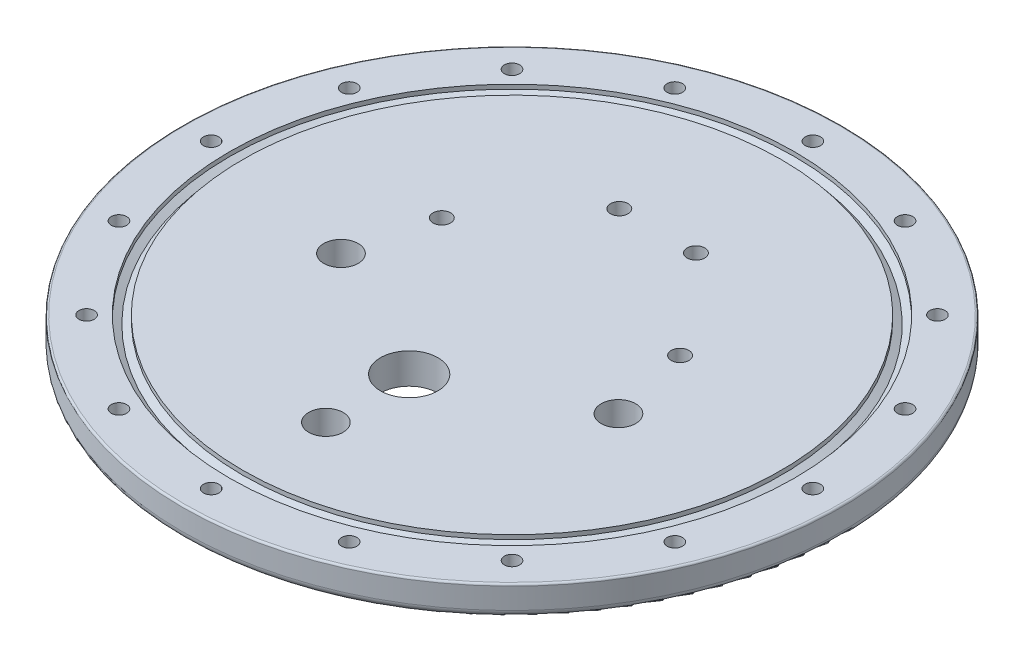
SolidWorks part; units mm, degrees
ref_plane "Front Plane" through (0, 0, 0) normal (0, 0, 1) x (1, 0, 0)
ref_plane "Top Plane" through (0, 0, 0) normal (0, 1, 0) x (1, 0, 0)
ref_plane "Right Plane" through (0, 0, 0) normal (1, 0, 0) x (0, 0, -1)
sketch "Sketch1" plane through (0, 0, 0) normal (0, 1, 0) x (1, 0, 0)
  circle A0 centre (0, 0) radius 86
  dimension "D1" = 172
extrude "Boss-Extrude1" add sketch "Sketch1" along normal blind 8 contours A0
sketch "Sketch2" plane through (0, 8, 0) normal (0, 1, 0) x (1, 0, 0)
  circle A1 centre (0, 78.5) radius 2
  circle A2 centre (30.0406, 72.5245) radius 2
  circle A3 centre (55.5079, 55.5079) radius 2
  circle A4 centre (72.5245, 30.0406) radius 2
  circle A5 centre (78.5, 0) radius 2
  circle A6 centre (72.5245, -30.0406) radius 2
  circle A7 centre (55.5079, -55.5079) radius 2
  circle A8 centre (30.0406, -72.5245) radius 2
  circle A9 centre (0, -78.5) radius 2
  circle A10 centre (-30.0406, -72.5245) radius 2
  circle A11 centre (-55.5079, -55.5079) radius 2
  circle A12 centre (-72.5245, -30.0406) radius 2
  circle A13 centre (-78.5, 0) radius 2
  circle A14 centre (-72.5245, 30.0406) radius 2
  circle A15 centre (-55.5079, 55.5079) radius 2
  circle A16 centre (-30.0406, 72.5245) radius 2
  circle A18 centre (0, 0) radius 78.5 construction
  point P38 (0, 0)
  dimension "D1" = 157
  dimension "D2" = 4
  dimension "D3" = 16
extrude "Cut-Extrude1" cut sketch "Sketch2" against normal up to next
sketch "Sketch6" plane through (0, 8, 0) normal (0, 1, 0) x (1, 0, 0)
  circle A0 centre (-10, 38) radius 2.3
  circle A1 centre (10, 38) radius 2.3
  circle A2 centre (-31.088, 12.7711) radius 2.3
  circle A3 centre (31.0922, 12.7711) radius 2.3
  dimension "D1" = 4.6
extrude "Cut-Extrude3" cut sketch "Sketch6" against normal offset from surface (6 mm away) 2 up to face at (0, 0, -76.5)
sketch "Sketch8" plane through (0, 8, 0) normal (0, 1, 0) x (1, 0, 0)
  circle A0 centre (-36.2, -8.4288) radius 4.5
  circle A1 centre (36.2, -8.4288) radius 4.5
  circle A2 centre (0, -48.5665) radius 4.5
  circle A3 centre (0, -26.8268) radius 7.5
  point P10 (0, -26.8268)
  dimension "D1" = 9
  dimension "D2" = 9
  dimension "D3" = 15
extrude "Cut-Extrude4" cut sketch "Sketch8" against normal up to next
sketch "Sketch4" plane through (0, 0, 0) normal (0, 0, 1) x (1, 0, 0)
  line L0 (0, 0) -> (72, 0) construction
  line L1 (-86, 0) -> (86, 0) construction
  line L2 (72, 0) -> (72, 8) construction
  line L3 (74.5245, 8) -> (70.5245, 8) construction
  line L5 (73.75, 6.8804) -> (73.75, 8)
  line L6 (73.75, 8) -> (70.25, 8)
  line L7 (70.25, 8) -> (70.25, 6.8804)
  line L9 (0, 0) -> (0, 12.8224) construction
  line L10 (70.25, 6.8804) -> (72, 5.87)
  line L11 (72, 5.87) -> (73.75, 6.8804)
  line L12 (72, 5.87) -> (72.8886, 5.87) construction
  dimension "D1" = 72
  dimension "D2" = 3.5
  dimension "D3" = 2.13
  dimension "D4" = 30
revolve "Cut-Revolve1" cut sketch "Sketch4" angle 360 about L9
sketch "Sketch10" plane through (0, 8, 0) normal (0, 1, 0) x (1, 0, 0)
  circle A0 centre (0, 0) radius 69.995
  dimension "D1" = 139.99
extrude "Cut-Extrude5" [suppressed] cut sketch "Sketch10" against normal offset from surface (30.1 mm away) 8
sketch "Sketch11" plane through (0, 0, 0) normal (0, 0, 1) x (1, 0, 0)
  line L0 (0, 0) -> (73, 0)
  line L1 (73, 0) -> (73, -7)
  line L2 (73, -7) -> (86, 6)
  line L3 (86, 6) -> (86, 0)
  line L4 (-86, 0) -> (86, 0) construction
  line L5 (73, 0) -> (86, 0)
  line L6 (73, -7) -> (77.1661, -7) construction
  line L10 (86, 8) -> (-86, 8) construction
  line L11 (86, 8) -> (-86, 8) construction
  line L12 (86, 0) -> (86, 8) construction
  dimension "D1" = 73
  dimension "D2" = 45
  dimension "D3" = 2
ref_axis "Axis1" through (0, 8, 0) along (0, -1, 0)
revolve "Cut-Revolve2" [suppressed] cut sketch "Sketch11" angle 360 about axis through (0, 8, 0) along (0, -1, 0)
fillet "Fillet1" radius 2 1 edges at (0, 0, 86)
fillet "Fillet2" radius 0.5 1 edges at (0, 8, 86)
